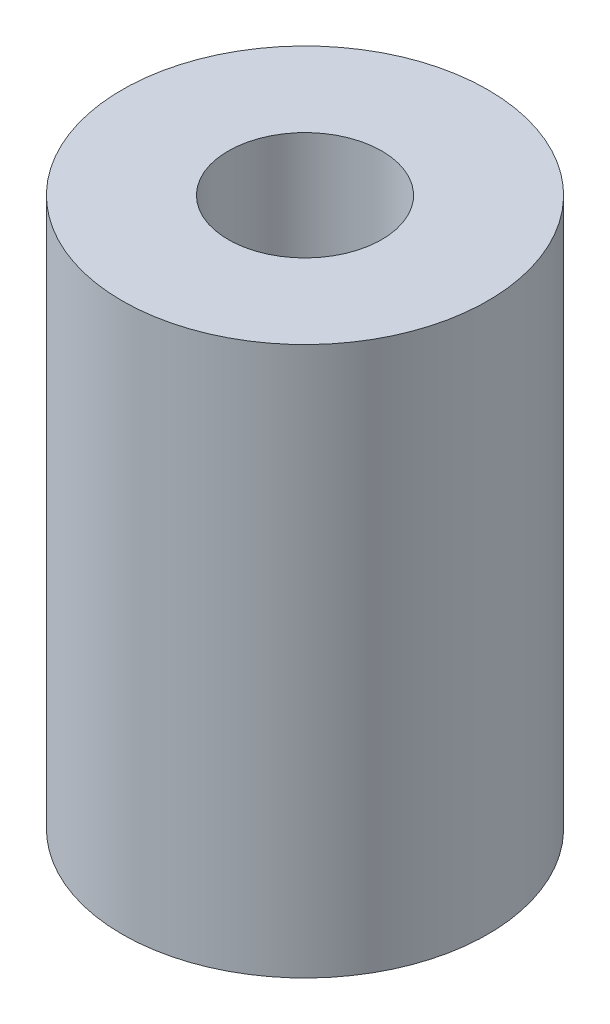
SolidWorks part; units mm, degrees
material "ABS"
ref_plane "Front Plane" through (0, 0, 0) normal (0, 0, 1) x (1, 0, 0)
ref_plane "Top Plane" through (0, 0, 0) normal (0, 1, 0) x (1, 0, 0)
ref_plane "Right Plane" through (0, 0, 0) normal (1, 0, 0) x (0, 0, -1)
sketch "Sketch1" plane through (0, 0, 0) normal (0, 1, 0) x (1, 0, 0)
  circle A0 centre (0, 0) radius 6.35
  circle A1 centre (0, 0) radius 2.667
  dimension "D1" = 12.7
  dimension "D2" = 5.334
extrude "Boss-Extrude1" add sketch "Sketch1" along normal blind 19.05
sketch "Sketch2" plane through (0, 0, 0) normal (0, -1, 0) x (-1, 0, 0)
  circle A0 centre (0, 0) radius 9.525
  circle A1 centre (0, 0) radius 2.54
  dimension "D1" = 19.05
extrude "Boss-Extrude2" [suppressed] add sketch "Sketch2" against normal blind 7.62
chamfer "Chamfer1" [suppressed] distance 3.175 angle 68
fillet "Fillet1" [suppressed] radius 12.7
sketch "Sketch3" plane through (0, 19.05, 0) normal (0, 1, 0) x (1, 0, 0)
  circle A0 centre (0, 0) radius 9.525
  circle A1 centre (0, 0) radius 2.54
  dimension "D1" = 19.05
extrude "Boss-Extrude3" [suppressed] add sketch "Sketch3" against normal blind 7.62
chamfer "Chamfer2" [suppressed] distance 3.175 angle 68
fillet "Fillet2" [suppressed] radius 12.7
sketch "Sketch4" plane through (0, 0, 0) normal (0, 0, 1) x (1, 0, 0)
  line L1 (-14.5993, 37.9681) -> (14.5993, 37.9681)
  line L2 (-14.5993, 37.9681) -> (-14.5993, -4.7123)
  line L3 (-14.5993, -4.7123) -> (14.5993, -4.7123)
  line L4 (14.5993, 37.9681) -> (14.5993, -4.7123)
  line L5 (-14.5993, 37.9681) -> (14.5993, -4.7123) construction
  line L6 (-14.5993, -4.7123) -> (14.5993, 37.9681) construction
  point P0 (0, 16.6279)
extrude "Cut-Extrude1" [suppressed] cut sketch "Sketch4" along normal through all from offset 6.35
